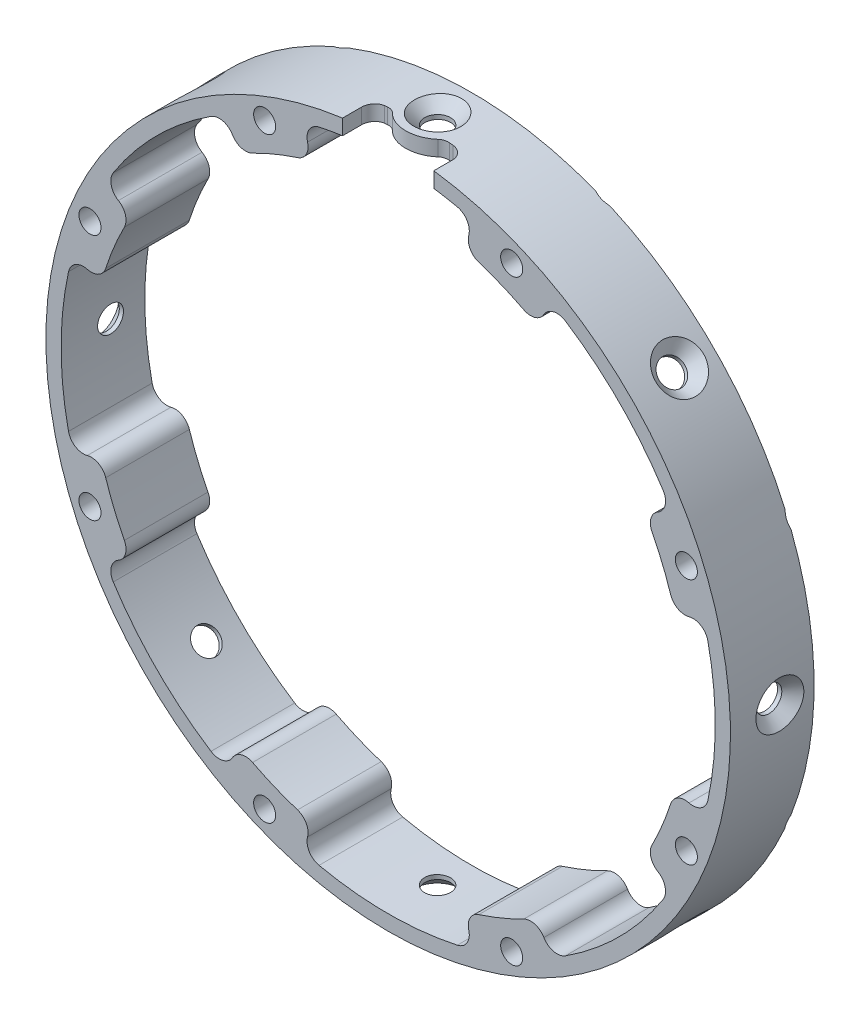
SolidWorks part; units mm, degrees
ref_plane "前视基准面" through (0, 0, 0) normal (0, 0, 1) x (1, 0, 0)
ref_plane "上视基准面" through (0, 0, 0) normal (0, 1, 0) x (1, 0, 0)
ref_plane "右视基准面" through (0, 0, 0) normal (1, 0, 0) x (0, 0, -1)
sketch "草图1" plane through (0, 0, 0) normal (0, 0, 1) x (1, 0, 0)
  line L0 (11.1292, 41.5348) -> (10.0939, 37.6711)
  line L17 (21.5, 37.2391) -> (19.5, 33.775)
  line L18 (-11.1292, 41.5348) -> (-10.0939, 37.6711)
  line L19 (37.2391, 21.5) -> (33.775, 19.5)
  line L20 (41.5348, 11.1292) -> (37.6711, 10.0939)
  line L21 (41.5348, -11.1292) -> (37.6711, -10.0939)
  line L22 (37.2391, -21.5) -> (33.775, -19.5)
  line L23 (21.5, -37.2391) -> (19.5, -33.775)
  line L24 (11.1292, -41.5348) -> (10.0939, -37.6711)
  line L25 (-11.1292, -41.5348) -> (-10.0939, -37.6711)
  line L26 (-21.5, -37.2391) -> (-19.5, -33.775)
  line L27 (-37.2391, -21.5) -> (-33.775, -19.5)
  line L28 (-41.5348, -11.1292) -> (-37.6711, -10.0939)
  line L29 (-41.5348, 11.1292) -> (-37.6711, 10.0939)
  line L30 (-37.2391, 21.5) -> (-33.775, 19.5)
  line L31 (-21.5, 37.2391) -> (-19.5, 33.775)
  circle A1 centre (0, 0) radius 45
  arc A3 (10.0939, 37.6711) -> (19.5, 33.775) centre (0, 0) cw
  arc A4 (11.1292, 41.5348) -> (-11.1292, 41.5348) centre (0, 0) ccw
  arc A21 (37.2391, 21.5) -> (21.5, 37.2391) centre (0, 0) ccw
  arc A22 (33.775, 19.5) -> (37.6711, 10.0939) centre (0, 0) cw
  arc A23 (41.5348, -11.1292) -> (41.5348, 11.1292) centre (0, 0) ccw
  arc A24 (37.6711, -10.0939) -> (33.775, -19.5) centre (0, 0) cw
  arc A25 (21.5, -37.2391) -> (37.2391, -21.5) centre (0, 0) ccw
  arc A26 (19.5, -33.775) -> (10.0939, -37.6711) centre (0, 0) cw
  arc A27 (-11.1292, -41.5348) -> (11.1292, -41.5348) centre (0, 0) ccw
  arc A28 (-10.0939, -37.6711) -> (-19.5, -33.775) centre (0, 0) cw
  arc A29 (-37.2391, -21.5) -> (-21.5, -37.2391) centre (0, 0) ccw
  arc A30 (-33.775, -19.5) -> (-37.6711, -10.0939) centre (0, 0) cw
  arc A31 (-41.5348, 11.1292) -> (-41.5348, -11.1292) centre (0, 0) ccw
  arc A32 (-37.6711, 10.0939) -> (-33.775, 19.5) centre (0, 0) cw
  arc A33 (-21.5, 37.2391) -> (-37.2391, 21.5) centre (0, 0) ccw
  arc A34 (-19.5, 33.775) -> (-10.0939, 37.6711) centre (0, 0) cw
  point P51 (0, 0)
  point P56 (0, 0)
  dimension "D1" = 8
extrude "凸台-拉伸1" add sketch "草图1" against normal blind 11
hole_wizard "M3 锥坑平头的锥孔2" positions "3D草图3" profile "草图4" countersink size "M3" standard "BSI" end condition through all
sketch3d "3D草图3"
  point P67 (31.8198, 31.8198, -6.5)
  point P76 (45, 0, -6.5)
  point P83 (31.8198, -31.8198, -6.5)
  point P85 (-31.8198, 31.8198, -6.5)
  point P87 (-31.8198, -31.8198, -6.5)
  point P96 (0, -45, -6.5)
  point P98 (0, 45, -6.5)
  point P105 (-45, 0, -6.5)
sketch "草图4" plane through (31.8198, 31.8198, -6.5) normal (0, 0, 1) x (-0.7071, 0.7071, 0)
  line L0 (0, 0) -> (0, 108.6396)
  line L1 (0, 108.6396) -> (1.7, 108.6396)
  line L2 (1.7, 108.6396) -> (1.7, 1.45)
  line L3 (1.7, 1.45) -> (3.15, 0)
  line L5 (3.15, 0) -> (0, 0)
  line L6 (-1.7, 1.45) -> (-3.15, 0) construction
  line L11 (0, -6.35) -> (0, 107.95) construction
  dimension "通孔孔直径" = 3.4
  dimension "通孔孔深度" = 108.6396
  dimension "近端锥形沉头孔直径" = 6.3
  dimension "近端锥形沉头孔角度" = 90
ref_plane "基准面1" through (0, 45, 0) normal (0, 1, 0) x (1, 0, 0)
sketch "草图7" plane through (0, 45, 0) normal (0, 1, 0) x (1, 0, 0)
  line L0 (-6, 0) -> (6, 0)
  line L1 (-45, 0) -> (45, 0) construction
  line L2 (6, 0) -> (6, 4)
  line L3 (6, 4) -> (3.3749, 4)
  line L5 (-6, 0) -> (-6, 4)
  line L6 (-6, 4) -> (-3.3749, 4)
  arc A1 (3.3749, 4) -> (-3.3749, 4) centre (0, 6.5) cw
extrude "切除-拉伸1" cut sketch "草图7" against normal up to next
hole_wizard "M2.5 锥坑平头的锥孔2" positions "3D草图4" profile "草图8" countersink size "M2.5" standard "BSI" end condition up to next
sketch3d "3D草图4"
  point P13 (39.2044, 16.239, -11)
  point P19 (16.239, 39.2044, -11)
  point P21 (-16.239, 39.2044, -11)
  point P23 (39.2044, -16.239, -11)
  point P26 (-39.2044, 16.239, -11)
  point P28 (-39.2044, -16.239, -11)
  point P30 (-16.239, -39.2044, -11)
  point P32 (16.239, -39.2044, -11)
sketch "草图8" plane through (39.2044, 16.239, -11) normal (1, 0, 0) x (0, 1, 0)
  line L0 (0, 0) -> (0, 11)
  line L1 (0, 11) -> (1.45, 11)
  line L2 (1.45, 11) -> (1.45, 1.3)
  line L3 (1.45, 1.3) -> (2.75, 0)
  line L5 (2.75, 0) -> (0, 0)
  line L6 (-1.45, 1.3) -> (-2.75, 0) construction
  line L11 (0, -6.35) -> (0, 107.95) construction
  dimension "通孔孔直径" = 2.9
  dimension "通孔孔深度" = 11
  dimension "近端锥形沉头孔直径" = 5.5
  dimension "近端锥形沉头孔角度" = 90
fillet "圆角1" radius 2 32 edges at (-41.5348, -11.1292, -5.5) (-37.6711, -10.0939, -5.5) (-33.775, -19.5, -5.5) (-37.2391, -21.5, -5.5) (-21.5, -37.2391, -5.5) (-10.0939, -37.6711, -5.5) (-19.5, -33.775, -5.5) (-11.1292, -41.5348, -5.5) (11.1292, -41.5348, -5.5) (10.0939, -37.6711, -5.5) (19.5, -33.775, -5.5) (21.5, -37.2391, -5.5) (37.2391, -21.5, -5.5) (33.775, -19.5, -5.5) (37.6711, -10.0939, -5.5) (41.5348, -11.1292, -5.5) (41.5348, 11.1292, -5.5) (37.6711, 10.0939, -5.5) (33.775, 19.5, -5.5) (37.2391, 21.5, -5.5) (21.5, 37.2391, -5.5) (11.1292, 41.5348, -5.5) (10.0939, 37.6711, -5.5) (19.5, 33.775, -5.5) (-11.1292, 41.5348, -5.5) (-10.0939, 37.6711, -5.5) (-21.5, 37.2391, -5.5) (-19.5, 33.775, -5.5) (-37.2391, 21.5, -5.5) (-33.775, 19.5, -5.5) (-37.6711, 10.0939, -5.5) (-41.5348, 11.1292, -5.5)
fillet "圆角2" radius 1.5 4 edges at (-6, 43.5888, -4) (6, 43.5888, -4) (-3.3749, 43.8703, -4) (3.3749, 43.8703, -4)
